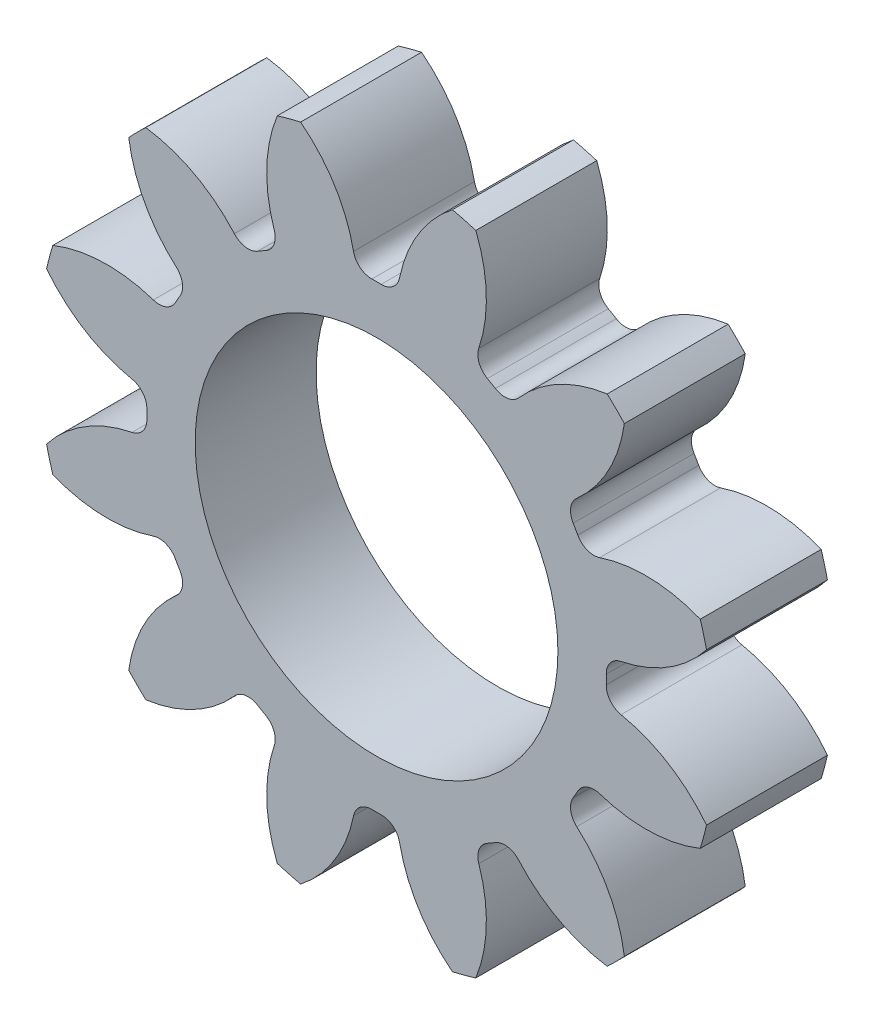
SolidWorks part; units mm, degrees
ref_plane "Front Plane" through (0, 0, 0) normal (0, 0, 1) x (1, 0, 0)
ref_plane "Top Plane" through (0, 0, 0) normal (0, 1, 0) x (1, 0, 0)
ref_plane "Right Plane" through (0, 0, 0) normal (1, 0, 0) x (0, 0, -1)
sketch "Sketch1" plane through (0, 0, 0) normal (0, 0, 1) x (1, 0, 0)
  line L4 (-0.8575, 9.4612) -> (0, 0) construction
  line L5 (0, 0) -> (0, 14) construction
  line L6 (0, 0) -> (3.6235, 13.523) construction
  line L7 (-1.6208, 11.89) -> (0.6878, 13.1053) construction
  line L8 (-1.6208, 11.89) -> (0.3858, 12.1636) construction
  line L11 (1.6208, 11.89) -> (-1.6208, 11.89) construction
  circle A0 centre (0, 0) radius 9.5
  circle A1 centre (0, 0) radius 12 construction
  circle A2 centre (0, 0) radius 14
  arc A3 (-3.1383, 13.6437) -> (-0.8575, 9.4612) centre (-6.8248, 8.9204) cw
  arc A4 (3.1383, 13.6437) -> (0.8575, 9.4612) centre (6.8248, 8.9204) ccw
  point P5 (-12, 0)
  point P6 (-14, 0)
  point P7 (-9.5, 0)
  point P12 (-1.6208, 11.89)
  point P22 (1.6208, 11.89)
  dimension "D5" = 24
  dimension "D1" = 2.5
  dimension "D2" = 2
  dimension "D3" = 20
  dimension "D4" = 3.2416
  dimension "D6" = 15
  dimension "D7" = 0.5
extrude "Boss-Extrude1" add sketch "Sketch1" against normal blind 5 contours A2
extrude "Cut-Extrude1" cut sketch "Sketch1<4>" against normal blind 10 contours A4 A2 A3 A0 region at (0, 12.2045, 0)
sketch "Sketch1<4>" plane through (0, 0, 0) normal (0, 0, 1) x (1, 0, 0) same geometry as "Sketch1"
fillet "Fillet2" radius 0.76 2 edges at (0.8575, 9.4612, -2.5) (-0.8575, 9.4612, -2.5)
ref_axis "Axis1" through (0, 0, 0) along (0, 0, 1)
pattern_circular "CirPattern2" count 12 over 360 about axis through (0, 0, 0) along (0, 0, 1) of "Cut-Extrude1", "Fillet2"
sketch "Sketch2" plane through (0, 0, 0) normal (0, 0, 1) x (1, 0, 0)
  circle A0 centre (0, 0) radius 7.5
  point P3 (0, 0)
  dimension "D1" = 15
extrude "Cut-Extrude2" cut sketch "Sketch2" against normal up to surface (5 mm away) up to face at (0, 0, -5)
equation "\"backlash\"= 0.1mm"
equation "\"module\"= 2mm"
equation "\"pressureAngle\"= 20deg"
equation "\"width\"= 10mm"
equation "\"D1@Sketch1\"= 1.25 * \"module\""
equation "\"D2@Sketch1\"=\"module\""
equation "\"D5@Sketch1\"=\"module\"*\"numberOfTeeth\""
equation "\"D1@Boss-Extrude1\"=\"width\"-5"
equation "\"D3@Sketch1\"=\"pressureAngle\""
equation "\"D1@Cut-Extrude1\"=\"width\""
equation "\"D1@CirPattern2\"=\"numberOfTeeth\""
equation "\"D1@Fillet2\"=0.38*\"module\""
equation "\"D4@Sketch1\"=pi*\"module\"/2+\"backlash\""
equation "\"numberOfTeeth\"= 12"
equation "\"D6@Sketch1\"=180/\"numberOfTeeth\""
equation "\"toothTipProfile\"= 1mm"
equation "\"D7@Sketch1\"=\"toothTipProfile\"/2"
equation "\"lengthOverallRack\"= pi * \"module\" * \"numberOfTeethRack\""
equation "\"numberOfTeethRack\"= 20"
